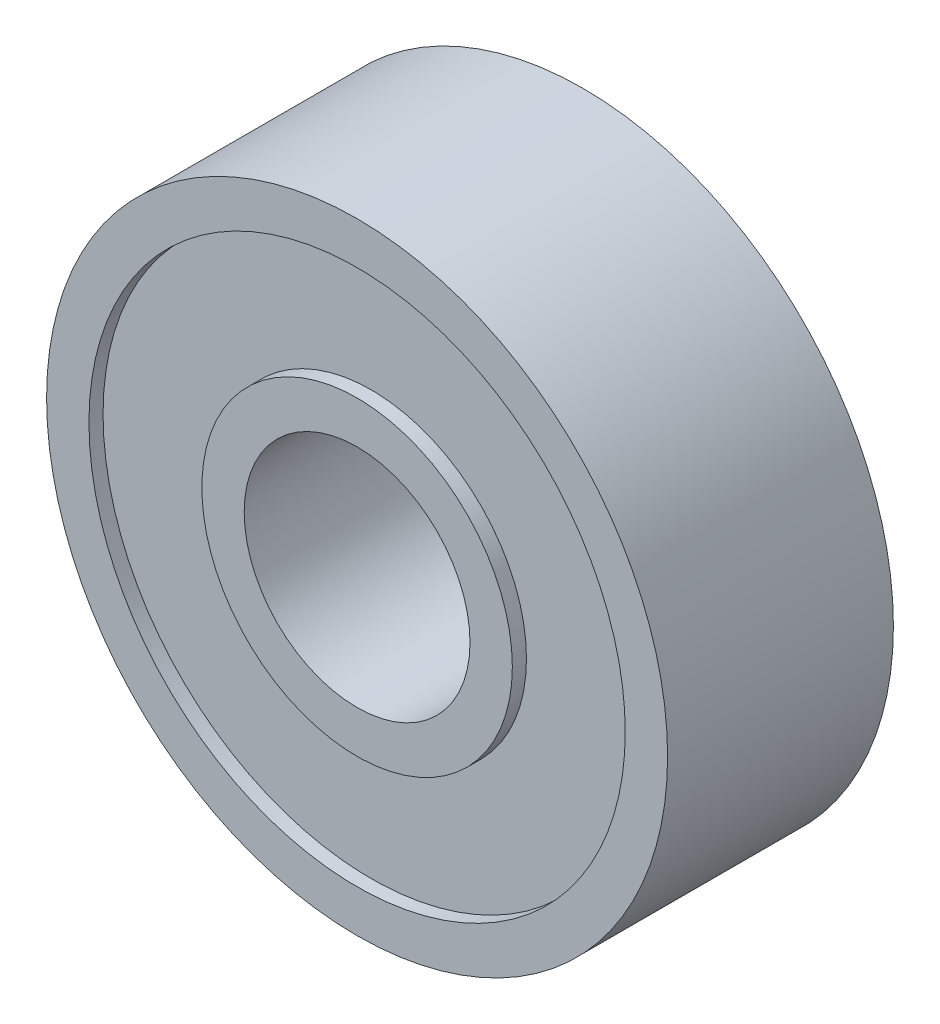
SolidWorks part; units mm, degrees
ref_plane "Alzado" through (0, 0, 0) normal (0, 0, 1) x (1, 0, 0)
ref_plane "Planta" through (0, 0, 0) normal (0, 1, 0) x (1, 0, 0)
ref_plane "Vista lateral" through (0, 0, 0) normal (1, 0, 0) x (0, 0, -1)
sketch "Croquis1" plane through (0, 0, 0) normal (0, 0, 1) x (1, 0, 0)
  circle A0 centre (0, 0) radius 11
  circle A1 centre (0, 0) radius 4
  circle A2 centre (0, 0) radius 9.5
  circle A3 centre (0, 0) radius 5.5
  dimension "D1" = 22
  dimension "D2" = 8
  dimension "D3" = 1.5
  dimension "D4" = 1.5
extrude "Saliente-Extruir1" add sketch "Croquis1" along normal blind 4 and the other way blind 4 contours A0 A2 | A3 A1 region at (-10.6889, 0, 0) region at (-5.3444, 0, 0)
extrude "Saliente-Extruir2" add sketch "Croquis1<4>" along normal blind 3.5 and the other way blind 3.5 contours A2 A3 region at (-9.2313, 0, 0)
sketch "Croquis1<4>" plane through (0, 0, 0) normal (0, 0, 1) x (1, 0, 0) same geometry as "Croquis1"
